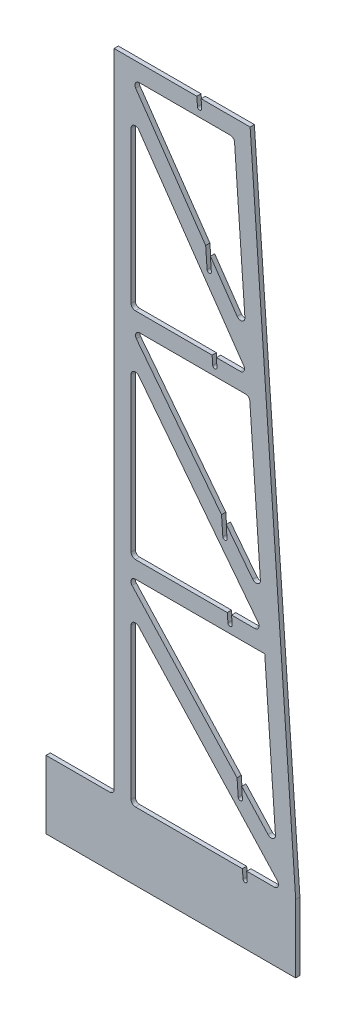
SolidWorks part; units mm, degrees
material "G10"
ref_plane "Front Plane" through (0, 0, 0) normal (0, 0, 1) x (1, 0, 0)
ref_plane "Top Plane" through (0, 0, 0) normal (0, 1, 0) x (1, 0, 0)
ref_plane "Right Plane" through (0, 0, 0) normal (1, 0, 0) x (0, 0, -1)
sketch "Sketch2" plane through (0, 0, 0) normal (0, 0, 1) x (1, 0, 0)
  line L0 (0, 0) -> (22.7266, 0)
  line L1 (34.7773, 260.35) -> (68.8026, 260.35)
  line L2 (0, 0) -> (0, 25.4)
  line L3 (74.0734, 26.0701) -> (55.1133, 294.9083) construction
  line L4 (70.3862, 258.8742) -> (74.2518, 204.063)
  line L5 (31.75, -2.8702) -> (31.75, 87.4083) construction
  line L6 (81.6573, 99.06) -> (85.653, 42.4047)
  line L7 (93.218, 25.4) -> (76.2, 266.7)
  line L8 (57.1027, 266.7) -> (57.3266, 263.525) construction
  line L9 (31.75, 26.9875) -> (31.75, 83.3398)
  line L10 (79.2219, 107.9708) -> (34.5916, 165.4752)
  line L11 (34.9916, 179.4933) -> (74.5051, 179.4933)
  line L12 (73.8153, 188.3336) -> (34.6433, 244.9978)
  line L13 (76.0887, 178.0175) -> (80.0382, 122.0171)
  line L14 (33.4715, 257.8598) -> (59.5955, 220.07)
  line L15 (72.5094, 185.8433) -> (63.6009, 185.8433)
  line L16 (33.7375, 176.9325) -> (65.5266, 135.9735)
  line L17 (77.9678, 105.41) -> (69.2736, 105.41)
  line L18 (33.274, 99.06) -> (81.6573, 99.06)
  line L19 (57.8984, 266.7) -> (58.1184, 263.5808)
  line L20 (31.75, 244.0951) -> (31.75, 187.4308)
  line L21 (31.75, 164.5019) -> (31.75, 106.9975)
  line L22 (32.106, 96.3973) -> (71.3223, 53.7963)
  line L23 (34.5055, 84.415) -> (86.3805, 28.0627)
  line L24 (31.75, 106.9975) -> (31.75, 260.7564) construction
  line L25 (56.307, 266.7) -> (56.5348, 263.4692)
  line L26 (85.2125, 25.4) -> (74.9164, 25.4)
  line L27 (93.218, 25.4) -> (93.218, 0)
  line L28 (25.4, 266.7) -> (25.4, 26.9875)
  line L29 (25.4, 0) -> (93.218, 0)
  line L30 (25.4, 266.7) -> (56.307, 266.7)
  line L31 (25.4, 0) -> (22.7266, 0) construction
  line L32 (57.8984, 266.7) -> (76.2, 266.7)
  line L33 (31.75, 25.4) -> (25.4414, 25.4) construction
  line L34 (60.4817, 218.788) -> (60.9203, 212.5703) construction
  line L35 (61.3677, 217.5064) -> (61.7132, 212.6075)
  line L36 (25.4, 0) -> (22.7266, 0)
  line L37 (23.8125, 25.4) -> (0, 25.4)
  line L38 (59.5955, 220.07) -> (60.1284, 212.5144)
  line L39 (62.8052, 185.8433) -> (63.0291, 182.6683) construction
  line L40 (63.6009, 185.8433) -> (63.8209, 182.7242)
  line L41 (62.0095, 185.8433) -> (62.2373, 182.6125)
  line L42 (66.235, 137.2116) -> (66.8036, 129.1497) construction
  line L43 (67.2771, 133.718) -> (67.5954, 129.2056)
  line L44 (65.5266, 135.9735) -> (66.0118, 129.0939)
  line L45 (68.3465, 107.2722) -> (68.7018, 102.235) construction
  line L46 (69.2736, 105.41) -> (69.4936, 102.2908)
  line L47 (67.6821, 105.41) -> (67.91, 102.1792)
  line L48 (72.0326, 55.0074) -> (72.5421, 47.7834) construction
  line L49 (73.0458, 51.9241) -> (73.3338, 47.8392)
  line L50 (71.3223, 53.7963) -> (71.7503, 47.7275)
  line L51 (74.0734, 26.0701) -> (74.3446, 22.225) construction
  line L52 (74.9164, 25.4) -> (75.1364, 22.2808)
  line L53 (73.325, 25.4) -> (73.5528, 22.1692)
  line L54 (61.3677, 217.5064) -> (71.3624, 203.0486)
  line L55 (62.0095, 185.8433) -> (33.3375, 185.8433)
  line L56 (73.325, 25.4) -> (33.3375, 25.4)
  line L57 (73.0458, 51.9241) -> (82.9014, 41.2178)
  line L58 (67.6821, 105.41) -> (33.3375, 105.41)
  line L59 (67.2771, 133.718) -> (77.2005, 120.9321)
  arc A0 (31.75, 83.3398) -> (34.5055, 84.415) centre (33.3375, 83.3398) cw
  arc A2 (79.2219, 107.9708) -> (77.9678, 105.41) centre (77.9678, 106.9975) cw
  arc A3 (33.274, 99.06) -> (32.106, 96.3973) centre (33.274, 97.4725) ccw
  arc A4 (85.653, 42.4047) -> (82.9014, 41.2178) centre (84.0694, 42.293) cw
  arc A5 (85.2125, 25.4) -> (86.3805, 28.0627) centre (85.2125, 26.9875) ccw
  arc A6 (31.75, 26.9875) -> (33.3375, 25.4) centre (33.3375, 26.9875) ccw
  arc A7 (56.5348, 263.4692) -> (58.1184, 263.5808) centre (57.3266, 263.525) ccw
  arc A9 (60.1284, 212.5144) -> (61.7132, 212.6075) centre (60.9203, 212.5703) ccw
  arc A10 (31.75, 106.9975) -> (33.3375, 105.41) centre (33.3375, 106.9975) ccw
  arc A11 (34.5916, 165.4752) -> (31.75, 164.5019) centre (33.3375, 164.5019) ccw
  arc A12 (77.2005, 120.9321) -> (80.0382, 122.0171) centre (78.4546, 121.9055) ccw
  arc A13 (34.9916, 179.4933) -> (33.7375, 176.9325) centre (34.9916, 177.9058) ccw
  arc A14 (76.0887, 178.0175) -> (74.5051, 179.4933) centre (74.5051, 177.9058) ccw
  arc A15 (73.8153, 188.3336) -> (72.5094, 185.8433) centre (72.5094, 187.4308) cw
  arc A16 (31.75, 187.4308) -> (33.3375, 185.8433) centre (33.3375, 187.4308) ccw
  arc A17 (31.75, 244.0951) -> (34.6433, 244.9978) centre (33.3375, 244.0951) cw
  arc A18 (34.7773, 260.35) -> (33.4715, 257.8598) centre (34.7773, 258.7625) ccw
  arc A19 (71.3624, 203.0486) -> (74.2518, 204.063) centre (72.6682, 203.9513) ccw
  arc A20 (68.8026, 260.35) -> (70.3862, 258.8742) centre (68.8026, 258.7625) cw
  arc A21 (23.8125, 25.4) -> (25.4, 26.9875) centre (23.8125, 26.9875) ccw
  arc A23 (62.2373, 182.6125) -> (63.8209, 182.7242) centre (63.0291, 182.6683) ccw
  arc A25 (66.0118, 129.0939) -> (67.5954, 129.2056) centre (66.8036, 129.1497) ccw
  arc A27 (67.91, 102.1792) -> (69.4936, 102.2908) centre (68.7018, 102.235) ccw
  arc A29 (71.7503, 47.7275) -> (73.3338, 47.8392) centre (72.5421, 47.7834) ccw
  arc A31 (73.5528, 22.1692) -> (75.1364, 22.2808) centre (74.3446, 22.225) ccw
  point P0 (0, 0)
  point P11 (81.2094, 105.41)
  point P34 (57.2146, 265.1125)
  point P58 (60.701, 215.6792)
  point P65 (62.9172, 184.2558)
  point P67 (81.2094, 105.41)
  point P70 (31.75, 105.41)
  point P73 (31.75, 169.1365)
  point P76 (80.406, 116.802)
  point P79 (31.75, 179.4933)
  point P82 (75.9846, 179.4933)
  point P85 (75.5368, 185.8433)
  point P90 (31.75, 249.1832)
  point P93 (31.75, 260.35)
  point P107 (66.5193, 133.1807)
  point P114 (68.5242, 104.7536)
  point P121 (72.2873, 51.3954)
  point P126 (74.209, 24.1476)
  dimension "D22" = 1.5875
  dimension "D23" = 1.5875
  dimension "D24" = 1.5875
  dimension "D25" = 1.5875
  dimension "D4" = 25.4
  dimension "D11" = 6.35
  dimension "D12" = 6.35
  dimension "D13" = 6.35
  dimension "D7" = 31.75
  dimension "D16" = 0
  dimension "D17" = 0
  dimension "D38" = 93.218
  dimension "D39" = 17.018
  dimension "D6" = 25.4
  dimension "D5" = 266.7
  dimension "D8" = 6.35
  dimension "D14" = 80.01
  dimension "D18" = 80.4333
  dimension "D9" = 6.35
  dimension "D10" = 6.35
  dimension "D15" = 6.35
  dimension "D20" = 6.35
  dimension "D19" = 25.4
  dimension "D42" = 7.874
  dimension "D43" = 7.9375
  dimension "D44" = 7.874
  dimension "D45" = 6.35
  dimension "D21" = 19.05
  dimension "D46" = 1.5875
  dimension "D47" = 3.175
  dimension "D48" = 1.5875
  dimension "D49" = 1.5875
  dimension "D50" = 1.5875
  dimension "D51" = 1.5875
  dimension "D52" = 1.5875
  dimension "D53" = 1.5875
  dimension "D54" = 3.175
  dimension "D55" = 3.175
  dimension "D56" = 3.175
  dimension "D57" = 3.175
  dimension "D58" = 3.175
  dimension "D59" = 3.175
extrude "Boss-Extrude2" add sketch "Sketch2" along normal blind 1.5875
ref_plane "Plane1" through (0, 0, 0.7937) normal (0, 0, 1) x (1, 0, 0)
ref_axis "Axis1" through (25.4, 26.9875, 0.7937) along (0, 1, 0)
